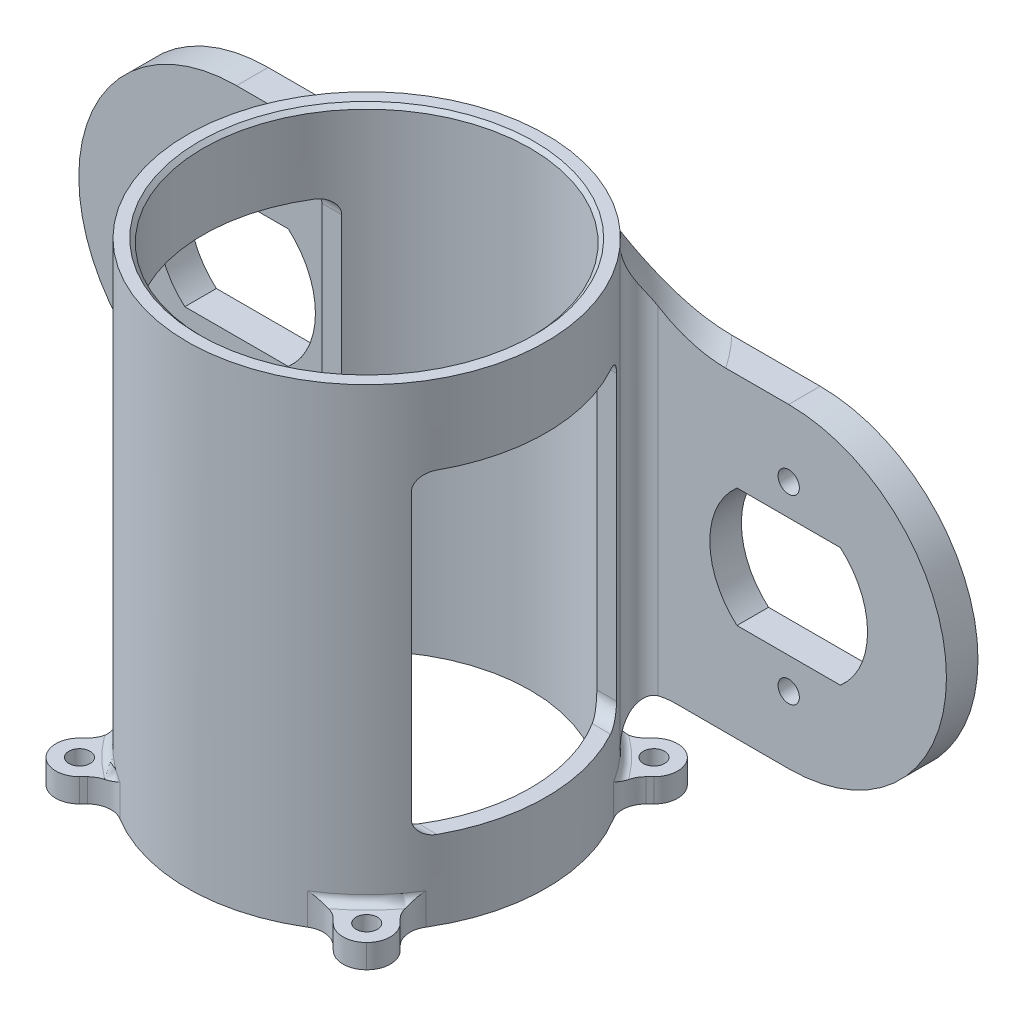
SolidWorks part; units mm, degrees
material "ABS"
ref_plane "Front Plane" through (0, 0, 0) normal (0, 0, 1) x (1, 0, 0)
ref_plane "Top Plane" through (0, 0, 0) normal (0, 1, 0) x (1, 0, 0)
ref_plane "Right Plane" through (0, 0, 0) normal (1, 0, 0) x (0, 0, -1)
sketch "Sketch1" plane through (0, 0, 0) normal (0, 0, 1) x (1, 0, 0)
  line L0 (-35, 0) -> (35, 0) construction
  line L1 (-35, 20) -> (35, 20)
  line L2 (-35, -20) -> (35, -20)
  arc A0 (-35, 20) -> (-35, -20) centre (-35, 0) ccw
  arc A1 (35, -20) -> (35, 20) centre (35, 0) ccw
  point P3 (0, 0)
  dimension "D2" = 20
  dimension "D1" = 70
extrude "Boss-Extrude1" add sketch "Sketch1" along normal blind 4
sketch "Sketch2" plane through (0, 0, 4) normal (0, 0, 1) x (1, 0, 0)
  line L0 (-41.5572, 7.55) -> (-28.4428, 7.55)
  line L1 (-41.5572, -7.55) -> (-28.4428, -7.55)
  line L4 (0, -24.6125) -> (0, 24.6125) construction
  line L5 (41.5572, 7.55) -> (28.4428, 7.55)
  line L6 (41.5572, -7.55) -> (28.4428, -7.55)
  circle A0 centre (-35, 0) radius 10
  circle A1 centre (35, 0) radius 10
  dimension "D1" = 20
  dimension "D2" = 15.1
extrude "Cut-Extrude1" cut sketch "Sketch2" against normal through all contours L0 A0 L1 | L5 A1 L6 region at (-35, 0, 4) region at (35, 0, 4)
sketch "Sketch3" plane through (0, -20, 0) normal (0, -1, 0) x (1, 0, 0)
  line L0 (0, 22.5) -> (0, 0) construction
  circle A0 centre (0, 22.5) radius 20.75
  circle A1 centre (0, 22.5) radius 22.75
  dimension "D1" = 41.5
  dimension "D3" = 2
  dimension "D2" = 22.5
extrude "Boss-Extrude2" add sketch "Sketch3" against normal blind 60
sketch "Sketch4" plane through (0, 20, 0) normal (0, 1, 0) x (1, 0, 0)
  circle A0 centre (0, -22.5) radius 20.75 construction
  circle A2 centre (0, -22.5) radius 20.75
extrude "Cut-Extrude2" cut sketch "Sketch4" against normal through all
sketch "Sketch5" plane through (0, -20, 0) normal (0, -1, 0) x (1, 0, 0)
  line L0 (0, 45.25) -> (0, 22.5) construction
  line L1 (-25, 35.5) -> (25, 35.5)
  line L2 (-25, 35.5) -> (-25, 9.5)
  line L3 (-25, 9.5) -> (25, 9.5)
  line L4 (25, 35.5) -> (25, 9.5)
  line L5 (0, 9.5) -> (0, 35.5) construction
  line L6 (-25, 22.5) -> (25, 22.5) construction
  line L8 (0, 22.5) -> (22.75, 22.5) construction
  arc A0 (13.2406, 4) -> (-13.2406, 4) centre (0, 22.5) ccw construction
  point P320 (0, 22.5)
  dimension "D1" = 50
  dimension "D2" = 26
extrude "Cut-Extrude3" cut sketch "Sketch5" against normal blind 40
sketch "Sketch6" plane through (0, -20, 0) normal (0, -1, 0) x (1, 0, 0)
  line L2 (-18.6698, 35.5) -> (-16.1729, 35.5)
  line L3 (16.1729, 35.5) -> (18.6698, 35.5)
  line L4 (-18.6698, 35.5) -> (-16.1729, 35.5)
  line L5 (16.1729, 35.5) -> (18.6698, 35.5)
  line L8 (18.6698, 9.5) -> (16.1729, 9.5)
  line L9 (-16.1729, 9.5) -> (-18.6698, 9.5)
  line L10 (-13.2406, 4) -> (-35, 4)
  line L11 (-35, 4) -> (-35, 0)
  line L12 (-35, 0) -> (-3.3634, 0)
  line L14 (35, 0) -> (35, 4)
  line L15 (35, 4) -> (13.2406, 4)
  line L16 (18.6698, 9.5) -> (16.1729, 9.5)
  line L17 (-16.1729, 9.5) -> (-18.6698, 9.5)
  line L27 (3.3634, 0) -> (35, 0)
  line L28 (3.3634, 0) -> (35, 0)
  arc A0 (18.6698, 9.5) -> (18.6698, 35.5) centre (0, 22.5) ccw construction
  arc A1 (16.1729, 9.5) -> (16.1729, 35.5) centre (0, 22.5) ccw construction
  arc A2 (18.6698, 35.5) -> (-18.6698, 35.5) centre (0, 22.5) ccw
  arc A3 (16.1729, 35.5) -> (-16.1729, 35.5) centre (0, 22.5) ccw
  arc A4 (13.2406, 4) -> (18.6698, 9.5) centre (0, 22.5) ccw
  arc A5 (-16.1729, 9.5) -> (16.1729, 9.5) centre (0, 22.5) ccw
  arc A6 (-18.6698, 9.5) -> (-13.2406, 4) centre (0, 22.5) ccw
  arc A7 (16.1729, 9.5) -> (16.1729, 35.5) centre (0, 22.5) ccw
  arc A8 (13.2406, 4) -> (18.6698, 9.5) centre (0, 22.5) ccw
  arc A9 (-16.1729, 9.5) -> (16.1729, 9.5) centre (0, 22.5) ccw
  arc A10 (-18.6698, 9.5) -> (-13.2406, 4) centre (0, 22.5) ccw
  arc A12 (18.6698, 35.5) -> (-18.6698, 35.5) centre (0, 22.5) ccw
  arc A13 (16.1729, 35.5) -> (-16.1729, 35.5) centre (0, 22.5) ccw
  arc A14 (-16.1729, 35.5) -> (-16.1729, 9.5) centre (0, 22.5) ccw construction
  arc A15 (-18.6698, 35.5) -> (-18.6698, 9.5) centre (0, 22.5) ccw construction
  arc A16 (18.6698, 9.5) -> (18.6698, 35.5) centre (0, 22.5) ccw
  arc A17 (16.1729, 9.5) -> (16.1729, 35.5) centre (0, 22.5) ccw
  arc A18 (-16.1729, 35.5) -> (-16.1729, 9.5) centre (0, 22.5) ccw
  arc A19 (-18.6698, 35.5) -> (-18.6698, 9.5) centre (0, 22.5) ccw
  circle A20 centre (0, 22.5) radius 22.75
  arc A25 (-3.3634, 0) -> (3.3634, 0) centre (0, 22.5) ccw
  arc A26 (-3.3634, 0) -> (3.3634, 0) centre (0, 22.5) ccw
  arc M17 (13.2406, 4) -> (18.6698, 9.5) centre (0, 22.5) ccw
  line M18 (18.6698, 9.5) -> (16.1729, 9.5)
  arc M19 (16.1729, 9.5) -> (-16.1729, 9.5) centre (0, 22.5) cw
  line M20 (-16.1729, 9.5) -> (-18.6698, 9.5)
  arc M21 (-18.6698, 9.5) -> (-13.2406, 4) centre (0, 22.5) ccw
  line M22 (-13.2406, 4) -> (-35, 4)
  line M23 (-35, 4) -> (-35, 0)
  line M24 (-35, 0) -> (-3.3634, 0)
  arc M25 (-3.3634, 0) -> (3.3634, 0) centre (0, 22.5) ccw
  line M26 (3.3634, 0) -> (35, 0)
  line M27 (35, 0) -> (35, 4)
  line M28 (35, 4) -> (13.2406, 4)
  dimension "D1" = 0
  dimension "D2" = 0
extrude "Boss-Extrude3" add sketch "Sketch6" along normal blind 10 contours M28 M17 M18 M19 M20 M21 M22 M23 M24 M25 M26 M27 | L4 A19 A18 M20 | A13 L5 A12 L4 | A17 A16 L5 M18 region at (0, -20, 44.8641) region at (-17.4214, -20, 35.2318) region at (21.4501, -20, 29.2323) region at (-17.4214, -20, 9.1141)
fillet "Fillet1" radius 10 2 edges at (-8.5395, 20, 1.4135) (8.5395, 20, 1.4135)
fillet "Fillet2" radius 2 2 edges at (-13.2406, 5, 4) (13.2406, 5, 4)
fillet "Fillet3" radius 2 8 edges at (17.4214, -20, 9.5) (17.4214, -20, 35.5) (17.4214, 20, 35.5) (17.4214, 20, 9.5) (-17.4214, -20, 35.5) (-17.4214, -20, 9.5) (-17.4214, 20, 9.5) (-17.4214, 20, 35.5)
sketch "Sketch9" plane through (0, -30, 0) normal (0, -1, 0) x (1, 0, 0)
  line L1 (-32.5, 49) -> (32.5, 49)
  line L2 (-32.5, 49) -> (-32.5, 24)
  line L6 (-32.5, 24) -> (32.5, 24)
  line L12 (32.5, 49) -> (32.5, 24)
  line L13 (0, 24) -> (0, 49) construction
  line L14 (-32.5, 36.5) -> (32.5, 36.5) construction
  circle A2 centre (0, 22.5) radius 22.75 construction
  point P160 (0, 36.5)
  dimension "D2" = 25
  dimension "D3" = 26.5
  dimension "D1" = 65
extrude "Boss-Extrude4" [suppressed] add sketch "Sketch9" against normal blind 4
sketch "Sketch10" [suppressed] plane through (0, -30, 0) normal (0, -1, 0) x (1, 0, 0)
  line L0 (-32.5, 49) -> (-32.5, 24) construction
  line L2 (-32.5, 49) -> (32.5, 49) construction
  line L4 (-27.5, 44) -> (-27.5, 36) construction
  line L6 (0, -26.95) -> (0, 26.95) construction
  line L7 (27.5, 44) -> (27.5, 36) construction
  circle A2 centre (-27.5, 44) radius 1.7
  circle A3 centre (-27.5, 36) radius 1.7
  circle A9 centre (27.5, 36) radius 1.7
  circle A10 centre (27.5, 44) radius 1.7
  dimension "D1" = 3.4
  dimension "D2" = 8
  dimension "D3" = 5
  dimension "D4" = 5
extrude "Cut-Extrude5" [suppressed] cut sketch "Sketch10" against normal up to next
fillet "Fillet5" [suppressed] radius 1
sketch "Sketch11" plane through (0, 40, 0) normal (0, 1, 0) x (1, 0, 0)
  circle A0 centre (0, -22.5) radius 20.75 construction
  circle A1 centre (0, -22.5) radius 22.75
  circle A2 centre (0, -22.5) radius 22.75
  circle A3 centre (0, -22.5) radius 20.75
  dimension "D1" = 0
extrude "Cut-Extrude6" cut sketch "Sketch11" against normal blind 10
fillet "Fillet8" [suppressed] radius 5
fillet "Fillet10" [suppressed] radius 3
sketch "Sketch15" plane through (0, 0, 4) normal (0, 0, 1) x (1, 0, 0)
  line L0 (-35, 11.5) -> (-35, 0) construction
  line L1 (-35, 0) -> (-18.6698, 0) construction
  line L2 (-18.6698, -18) -> (-18.6698, 18) construction
  line L3 (0, -25.025) -> (0, 25.025) construction
  circle A0 centre (-35, 11.5) radius 1.35
  circle A1 centre (35, 11.5) radius 1.35
  circle A2 centre (35, -11.5) radius 1.35
  circle A3 centre (-35, -11.5) radius 1.35
  dimension "D1" = 2.7
  dimension "D2" = 11.5
extrude "Cut-Extrude8" cut sketch "Sketch15" against normal through all
sketch "Sketch16" plane through (0, -30, 0) normal (0, -1, 0) x (1, 0, 0)
  line L0 (0, 0) -> (0, 22.5) construction
  line L1 (0, 22.5) -> (22.75, 22.5) construction
  line L3 (21.75, 25.5) -> (28.75, 25.5) construction
  line L4 (21.75, 25.5) -> (21.75, 19.5) construction
  line L5 (21.75, 19.5) -> (28.75, 19.5) construction
  line L6 (28.75, 25.5) -> (28.75, 19.5) construction
  line L7 (25.25, 19.5) -> (25.25, 25.5) construction
  line L8 (21.75, 22.5) -> (28.75, 22.5) construction
  line L12 (17.5009, 9.2417) -> (22.4506, 4.292)
  line L13 (17.5009, 9.2417) -> (13.2583, 4.9991)
  line L18 (13.2583, 4.9991) -> (18.208, 0.0494)
  line L19 (22.4506, 4.292) -> (18.208, 0.0494)
  line L24 (15.7331, 2.5242) -> (19.9758, 6.7669) construction
  line L25 (15.3796, 7.1204) -> (20.3293, 2.1707) construction
  line L42 (3, 0.75) -> (3, -6.25) construction
  line L43 (3, 0.75) -> (-3, 0.75) construction
  line L44 (-3, 0.75) -> (-3, -6.25) construction
  line L45 (3, -6.25) -> (-3, -6.25) construction
  line L46 (-3, -2.75) -> (3, -2.75) construction
  line L47 (0, 0.75) -> (0, -6.25) construction
  line L48 (-13.2583, 4.9991) -> (-18.208, 0.0494)
  line L49 (-13.2583, 4.9991) -> (-17.5009, 9.2417)
  line L50 (-17.5009, 9.2417) -> (-22.4506, 4.292)
  line L51 (-18.208, 0.0494) -> (-22.4506, 4.292)
  line L52 (-19.9758, 6.7669) -> (-15.7331, 2.5242) construction
  line L53 (-15.3796, 7.1204) -> (-20.3293, 2.1707) construction
  line L54 (-21.75, 19.5) -> (-28.75, 19.5) construction
  line L55 (-21.75, 19.5) -> (-21.75, 25.5) construction
  line L60 (-21.75, 25.5) -> (-28.75, 25.5) construction
  line L61 (-28.75, 19.5) -> (-28.75, 25.5) construction
  line L62 (-25.25, 25.5) -> (-25.25, 19.5) construction
  line L63 (-21.75, 22.5) -> (-28.75, 22.5) construction
  line L64 (-17.5009, 35.7583) -> (-22.4506, 40.708)
  line L65 (-17.5009, 35.7583) -> (-13.2583, 40.0009)
  line L66 (-13.2583, 40.0009) -> (-18.208, 44.9506)
  line L67 (-22.4506, 40.708) -> (-18.208, 44.9506)
  line L76 (-15.7331, 42.4758) -> (-19.9758, 38.2331) construction
  line L77 (-15.3796, 37.8796) -> (-20.3293, 42.8293) construction
  line L81 (-3, 44.25) -> (-3, 51.25) construction
  line L82 (-3, 44.25) -> (3, 44.25) construction
  line L83 (3, 44.25) -> (3, 51.25) construction
  line L84 (-3, 51.25) -> (3, 51.25) construction
  line L85 (3, 47.75) -> (-3, 47.75) construction
  line L86 (0, 44.25) -> (0, 51.25) construction
  line L87 (13.2583, 40.0009) -> (18.208, 44.9506)
  line L88 (13.2583, 40.0009) -> (17.5009, 35.7583)
  line L89 (17.5009, 35.7583) -> (22.4506, 40.708)
  line L90 (18.208, 44.9506) -> (22.4506, 40.708)
  line L91 (19.9758, 38.2331) -> (15.7331, 42.4758) construction
  line L92 (15.3796, 37.8796) -> (20.3293, 42.8293) construction
  circle A0 centre (0, 22.5) radius 22.75 construction
  point P6 (0, 22.5)
  point P7 (-19.1434, 6.4523)
  point P17 (0, 22.5)
  point P22 (-17.2747, 40.1439)
  point P24 (16.4661, 39.7266)
  point P28 (17.8544, 4.6456)
  point P37 (0, -2.75)
  point P46 (-17.8544, 4.6456)
  point P55 (-25.25, 22.5)
  point P64 (-17.8544, 40.3544)
  point P73 (0, 47.75)
  point P82 (17.8544, 40.3544)
  point P83 (0, 22.5)
  point P85 (0, 22.5)
  point P121 (25.25, 22.5)
  dimension "D1" = 6
  dimension "D3" = 8
  dimension "D2" = 7
  dimension "D4" = 1
extrude "Boss-Extrude7" add sketch "Sketch16" against normal blind 3
fillet "Fillet12" radius 3 16 edges at (-18.0675, -28.5, 8.6751) (-22.4506, -28.5, 4.292) (-18.208, -28.5, 0.0494) (-13.8249, -28.5, 4.4325) (13.8249, -28.5, 4.4325) (18.208, -28.5, 0.0494) (22.4506, -28.5, 4.292) (18.0675, -28.5, 8.6751) (18.0675, -28.5, 36.3249) (22.4506, -28.5, 40.708) (18.208, -28.5, 44.9506) (13.8249, -28.5, 40.5675) (-13.8249, -28.5, 40.5675) (-18.208, -28.5, 44.9506) (-22.4506, -28.5, 40.708) (-18.0675, -28.5, 36.3249)
sketch "Sketch17" plane through (0, -27, 0) normal (0, 1, 0) x (1, 0, 0)
  line L0 (-18.208, -4.292) -> (0, -22.5) construction
  line L1 (0, -22.5) -> (-18.208, -40.708) construction
  line L2 (0, 0) -> (0, -22.5) construction
  circle A11 centre (-18.208, -40.708) radius 1.35
  circle A12 centre (-18.208, -4.292) radius 1.35
  circle A13 centre (18.208, -4.292) radius 1.35
  circle A14 centre (18.208, -40.708) radius 1.35
  point P11 (0, -22.5)
  dimension "D1" = 2.7
  dimension "D2" = 135
extrude "Cut-Extrude9" cut sketch "Sketch17" against normal blind 3
fillet "Fillet13" radius 1 4 edges at (16.0867, -27, 6.4133) (16.0867, -27, 38.5867) (-16.0867, -27, 38.5867) (-16.0867, -27, 6.4133)
chamfer "Chamfer1" distance 0.5 angle 45 1 edges at (-20.75, 30, 22.5)
fillet "Fillet14" radius 5 2 edges at (-10.8015, -20, 2.4778) (10.8015, -20, 2.4778)
